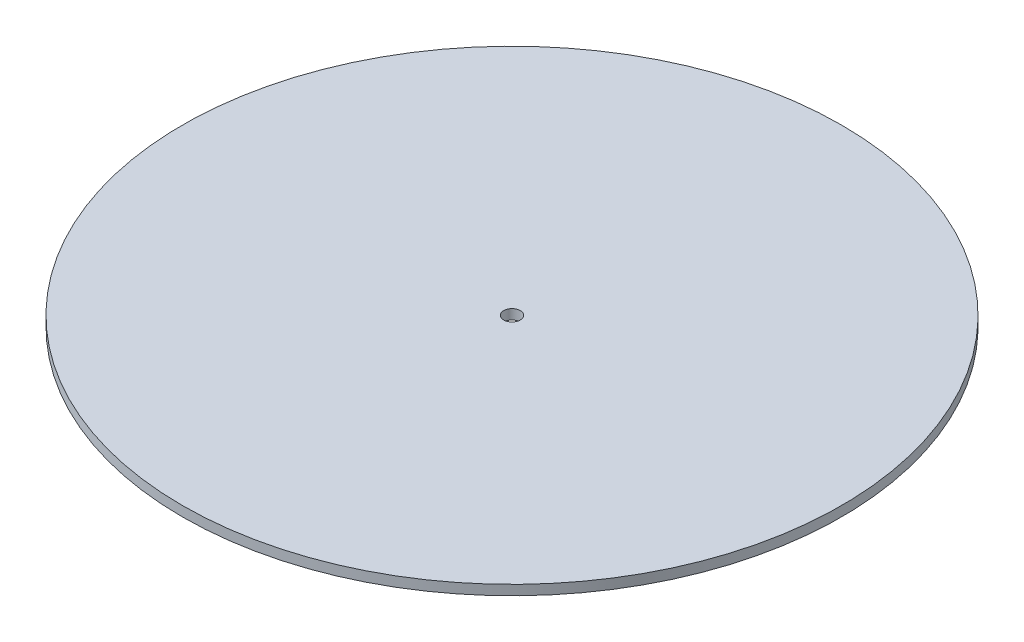
SolidWorks part; units mm, degrees
ref_plane "Front Plane" through (0, 0, 0) normal (0, 0, 1) x (1, 0, 0)
ref_plane "Top Plane" through (0, 0, 0) normal (0, 1, 0) x (1, 0, 0)
ref_plane "Right Plane" through (0, 0, 0) normal (1, 0, 0) x (0, 0, -1)
ref_axis "Axe1" through (0, 55, 0) along (0, -1, 0)
sketch "Esquisse2" plane through (0, 0, 0) normal (0, 0, 1) x (1, 0, 0)
  line L0 (0, 0) -> (100, 0)
  line L1 (100, 0) -> (100, 3)
  line L4 (100, 3) -> (0, 3)
  line L5 (0, 55) -> (0, -55) construction
  line L6 (0, 3) -> (0, 0)
  dimension "D1" = 100
  dimension "D3" = 3
revolve "Révolution1" add sketch "Esquisse2" angle 360 about axis through (0, 55, 0) along (0, -1, 0)
sketch "Esquisse4" plane through (0, 3, 0) normal (0, 1, 0) x (1, 0, 0)
  circle A0 centre (0, 0) radius 2.5
  dimension "D1" = 5
extrude "Enlèv. mat.-Extru.6" cut sketch "Esquisse4" against normal through all
